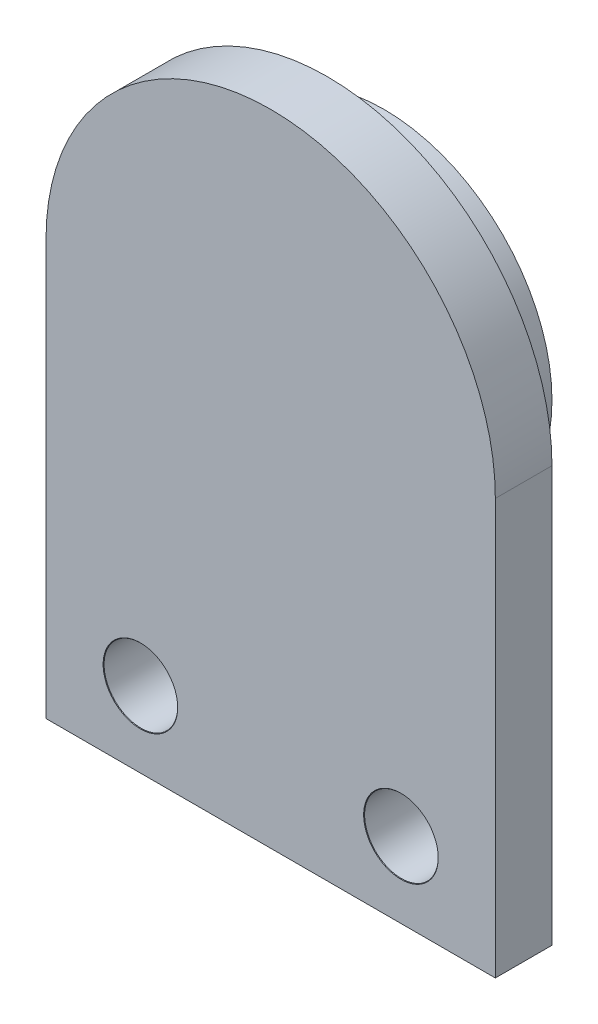
SolidWorks part; units mm, degrees
ref_plane "Front Plane" through (0, 0, 0) normal (0, 0, 1) x (1, 0, 0)
ref_plane "Top Plane" through (0, 0, 0) normal (0, 1, 0) x (1, 0, 0)
ref_plane "Right Plane" through (0, 0, 0) normal (1, 0, 0) x (0, 0, -1)
sketch "Sketch1" plane through (0, 0, 0) normal (0, 0, 1) x (1, 0, 0)
  line L0 (-11.9, 0) -> (-11.9, -22)
  line L1 (-11.9, -22) -> (11.9, -22)
  line L2 (11.9, -22) -> (11.9, 0)
  arc A0 (11.9, 0) -> (-11.9, 0) centre (0, 0) ccw
  dimension "D1" = 22
  dimension "D2" = 23.8
extrude "Boss-Extrude1" add sketch "Sketch1" along normal blind 3
sketch "Sketch2" plane through (0, 0, 0) normal (0, 0, -1) x (-1, 0, 0)
  circle A0 centre (0, 0) radius 8.9
  dimension "D1" = 17.8
extrude "Boss-Extrude2" add sketch "Sketch2" along normal blind 3
sketch "Sketch3" plane through (0, 0, -3) normal (0, 0, -1) x (-1, 0, 0)
  circle A0 centre (0, 0) radius 2
  dimension "D1" = 4
extrude "Boss-Extrude3" add sketch "Sketch3" along normal blind 3
hole_wizard "M3.5 Clearance Hole1" positions "3DSketch1" profile "Sketch5" hole size "M3.5" standard "ANSI Metric" end condition through all
sketch3d "3DSketch1"
  line L0 (-11.9, -22, 3) -> (11.9, -22, 3) construction
  line L1 (-11.9, 0, 3) -> (-11.9, -22, 3) construction
  line L2 (11.9, -22, 3) -> (11.9, 0, 3) construction
  point P0 (-6.9, -18, 3)
  point P2 (6.9, -18, 3)
  dimension "D1" = 4
  dimension "D2" = 5
  dimension "D3" = 5
sketch "Sketch5" plane through (-6.9, -18, 3) normal (1, 0, 0) x (0, -1, 0)
  line L0 (0, 0) -> (0, 9)
  line L1 (0, 9) -> (1.95, 9)
  line L2 (1.95, 9) -> (1.95, 0.025)
  line L3 (1.95, 0.025) -> (1.975, 0)
  line L5 (1.975, 0) -> (0, 0)
  line L6 (-1.95, 0.025) -> (-1.975, 0) construction
  line L11 (0, -6.35) -> (0, 107.95) construction
  dimension "Thru Hole Dia." = 3.9
  dimension "Thru Hole Depth" = 9
  dimension "Near C'Sink Dia." = 3.95
  dimension "Near C'Sink Angle" = 90
